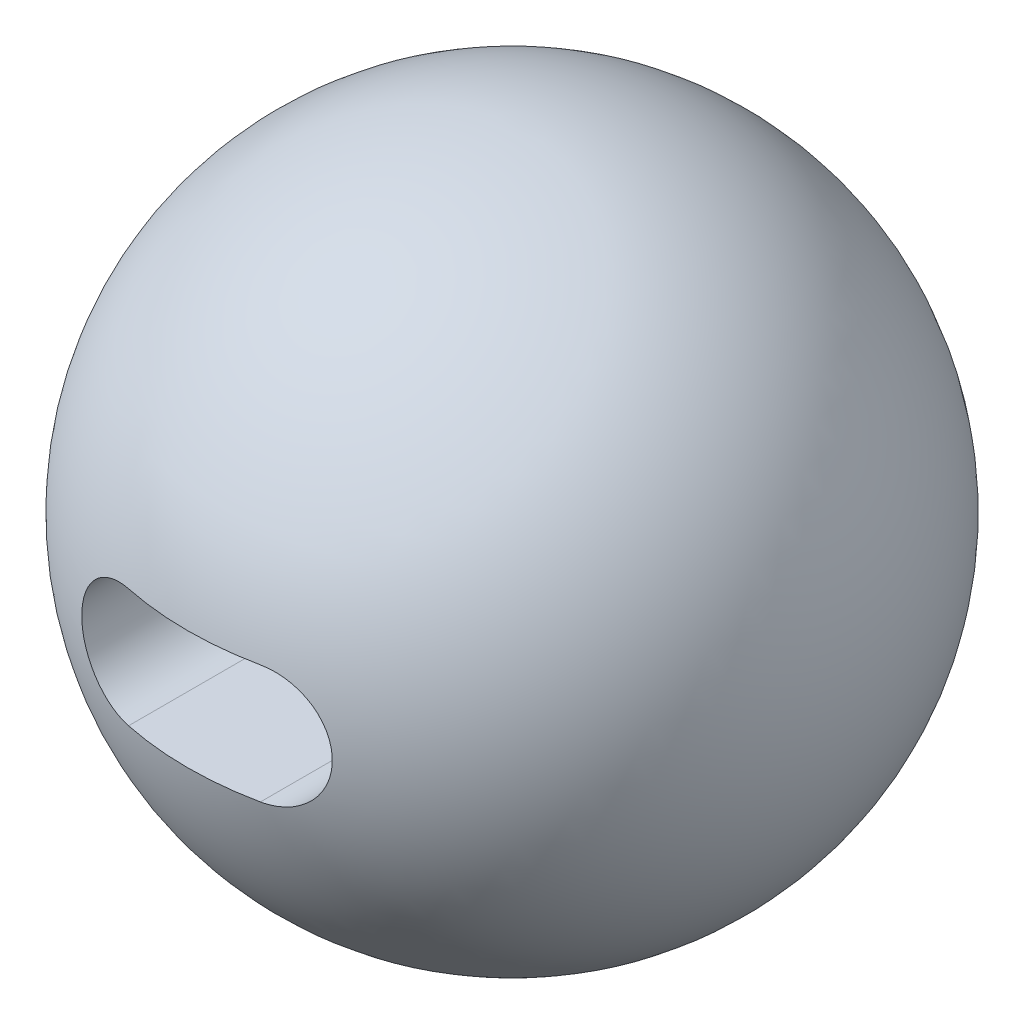
SolidWorks part; units mm, degrees
ref_plane "Front Plane" through (0, 0, 0) normal (0, 0, 1) x (1, 0, 0)
ref_plane "Top Plane" through (0, 0, 0) normal (0, 1, 0) x (1, 0, 0)
ref_plane "Right Plane" through (0, 0, 0) normal (1, 0, 0) x (0, 0, -1)
sketch "Sketch1" plane through (0, 0, 0) normal (0, 0, 1) x (1, 0, 0)
  line L0 (0, -500) -> (0, 500)
  arc A0 (0, 500) -> (0, -500) centre (0, 0) ccw
  point P6 (0, 0)
  dimension "D1" = 1000
revolve "Revolve1" add sketch "Sketch1" angle 360 about L0
ref_plane "Plane2" through (0, 0, 500) normal (0, 0, 1) x (1, 0, 0)
sketch "Sketch7" plane through (0, 0, 500) normal (0, 0, 1) x (1, 0, 0)
  line L0 (-100, 0) -> (100, 0) construction
  line L1 (-100, 90) -> (100, 90)
  line L2 (-100, -90) -> (100, -90)
  arc A0 (-100, 90) -> (-100, -90) centre (-100, 0) ccw
  arc A1 (100, -90) -> (100, 90) centre (100, 0) ccw
  point P3 (0, 0)
  point P8 (0, 0)
  dimension "D2" = 90
  dimension "D1" = 200
extrude "Cut-Extrude2" cut sketch "Sketch7" against normal blind 500
